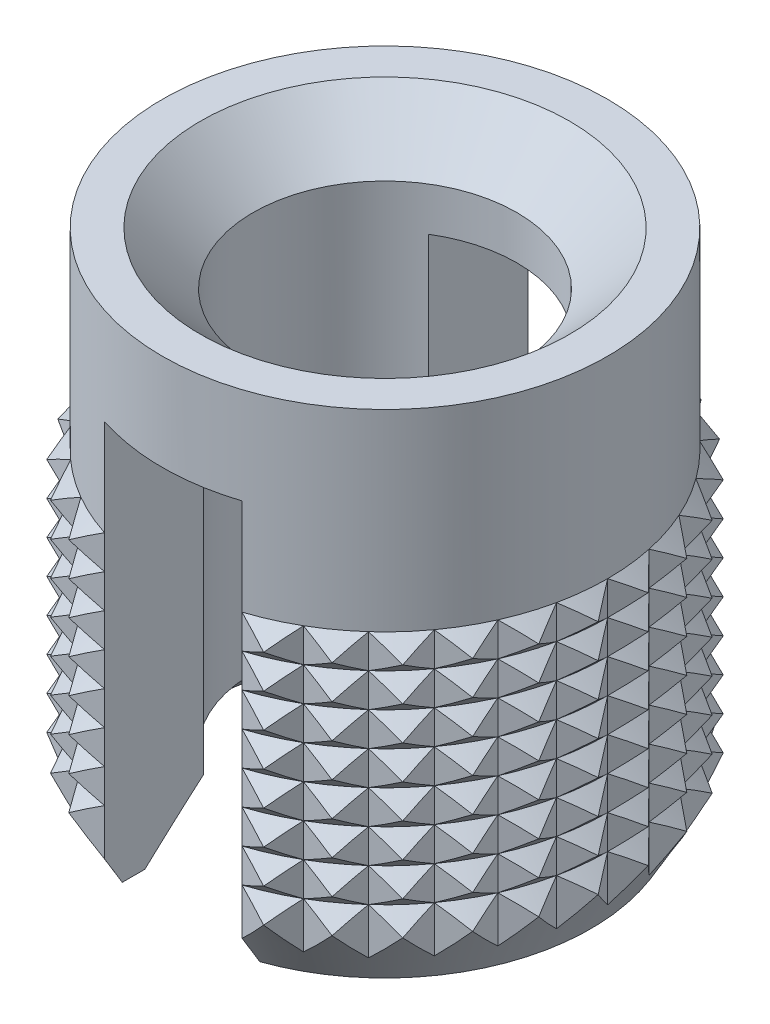
SolidWorks part; units mm, degrees
ref_plane "Front Plane" through (0, 0, 0) normal (0, 0, 1) x (1, 0, 0)
ref_plane "Top Plane" through (0, 0, 0) normal (0, 1, 0) x (1, 0, 0)
ref_plane "Right Plane" through (0, 0, 0) normal (1, 0, 0) x (0, 0, -1)
sketch "Sketch2" plane through (0, 0, 0) normal (0, 0, 1) x (1, 0, 0)
  line L0 (-2.11, 4.78) -> (-2.11, 2.9543)
  line L1 (-2.11, 2.9543) -> (-2.27, 2.7943)
  line L3 (-2.27, 0.5543) -> (-1.95, 0)
  line L4 (-1.95, 0) -> (-1.75, 0)
  line L5 (-1.75, 0) -> (-1.25, 0.5)
  line L6 (-1.25, 0.5) -> (-1.25, 4.28)
  line L7 (-1.25, 4.28) -> (-1.75, 4.78)
  line L8 (-1.75, 4.78) -> (-2.11, 4.78)
  line L9 (0, 0) -> (0, 4.78) construction
  line L10 (-2.27, 2.7943) -> (-2.11, 2.6343)
  line L11 (-2.11, 2.6343) -> (-2.27, 2.4743)
  line L12 (-2.27, 2.4743) -> (-2.11, 2.3143)
  line L13 (-2.11, 2.3143) -> (-2.27, 2.1543)
  line L14 (-2.27, 2.1543) -> (-2.11, 1.9943)
  line L15 (-2.11, 1.9943) -> (-2.27, 1.8343)
  line L16 (-2.27, 1.8343) -> (-2.11, 1.6743)
  line L17 (-2.11, 1.6743) -> (-2.27, 1.5143)
  line L18 (-2.27, 1.5143) -> (-2.11, 1.3543)
  line L19 (-2.11, 1.3543) -> (-2.27, 1.1943)
  line L20 (-2.27, 1.1943) -> (-2.11, 1.0343)
  line L21 (-2.11, 1.0343) -> (-2.27, 0.8743)
  line L22 (-2.27, 0.8743) -> (-2.11, 0.7143)
  line L23 (-2.11, 0.7143) -> (-2.27, 0.5543)
  point P20 (-2.11, 0.2771)
  dimension "D1" = 4.78
  dimension "D2" = 1.25
  dimension "D3" = 1.75
  dimension "D4" = 135
  dimension "D5" = 120
  dimension "D6" = 2.11
  dimension "D7" = 0.2
revolve "Revolve1" add sketch "Sketch2" angle 360 about L9
sketch "Sketch3" plane through (0, 4.78, 0) normal (0, 1, 0) x (1, 0, 0)
  line L0 (-0.2206, 2.0984) -> (0, 2.27)
  line L1 (0, 2.27) -> (0.2206, 2.0984)
  line L2 (-0.2206, 2.0984) -> (0, 0) construction
  line L3 (0, 0) -> (0.2206, 2.0984) construction
  line L4 (-0.2206, 2.0984) -> (-0.2892, 2.7511)
  line L5 (-0.2892, 2.7511) -> (0.2892, 2.7511)
  line L6 (0.2892, 2.7511) -> (0.2206, 2.0984)
  circle A0 centre (0, 0) radius 2.11 construction
  circle A3 centre (0, 0) radius 2.27 construction
  dimension "D1" = 12
extrude "Cut-Extrude1" cut sketch "Sketch3" against normal through all both and the other way through all
pattern_circular "CirPattern1" count 30 over 360 about axis through (0, 0, 0) along (0, -1, 0) of "Cut-Extrude1" reverse direction yes
sketch "Sketch4" plane through (0, 0, 0) normal (0, 0, 1) x (1, 0, 0)
  line L1 (-0.652, 3.8671) -> (0.652, 3.8671)
  line L2 (0.652, 3.8671) -> (0.652, 2.9543)
  line L3 (0.652, 2.9543) -> (0.652, 0)
  line L4 (0.652, 0) -> (-0.652, 0)
  line L5 (-0.652, 0) -> (-0.652, 3.8671)
  line L6 (0.652, 3.8671) -> (2.11, 3.8671) construction
  line L7 (2.11, 2.9543) -> (2.11, 4.78) construction
  line L8 (-1.95, 0) -> (1.95, 0) construction
extrude "Cut-Extrude2" cut sketch "Sketch4" against normal through all both and the other way through all
